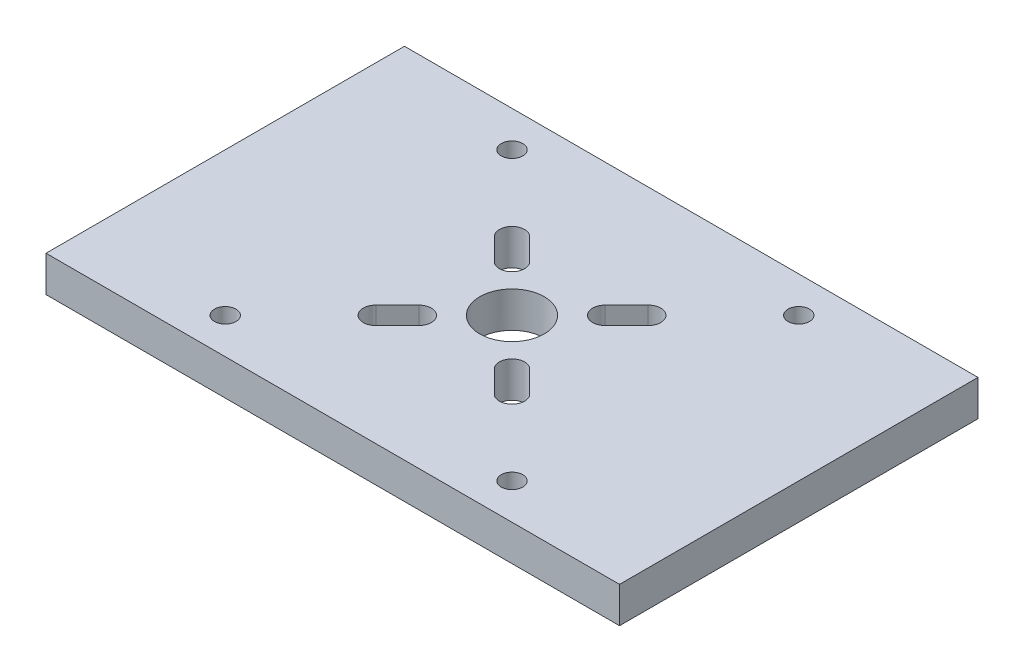
SolidWorks part; units mm, degrees
ref_plane "Front Plane" through (0, 0, 0) normal (0, 0, 1) x (1, 0, 0)
ref_plane "Top Plane" through (0, 0, 0) normal (0, 1, 0) x (1, 0, 0)
ref_plane "Right Plane" through (0, 0, 0) normal (1, 0, 0) x (0, 0, -1)
sketch "Sketch1" plane through (0, 0, 0) normal (0, 1, 0) x (1, 0, 0)
  line L1 (80, 50) -> (-80, 50)
  line L2 (80, 50) -> (80, -50)
  line L3 (80, -50) -> (-80, -50)
  line L4 (-80, 50) -> (-80, -50)
  line L5 (80, 50) -> (-80, -50) construction
  line L6 (80, -50) -> (-80, 50) construction
  point P0 (0, 0)
  dimension "D1" = 160
  dimension "D2" = 100
extrude "base" add sketch "Sketch1" along normal blind 10 contours L1 L4 L3 L2
sketch "Sketch2" plane through (0, 10, 0) normal (0, 1, 0) x (1, 0, 0)
  circle A0 centre (0, 0) radius 9
  dimension "D1" = 18
extrude "actuator cut" cut sketch "Sketch2" against normal blind 40
sketch "Sketch3" plane through (0, 10, 0) normal (0, 1, 0) x (1, 0, 0)
  line L0 (19, -19) -> (13, -13) construction
  line L1 (0, 0) -> (0, 19) construction
  line L2 (-19, -19) -> (19, 19) construction
  line L3 (-19, -19) -> (-13, -13) construction
  line L4 (-21.4749, -16.5251) -> (-15.4749, -10.5251)
  line L5 (-16.5251, -21.4749) -> (-10.5251, -15.4749)
  line L6 (21.4749, -16.5251) -> (15.4749, -10.5251)
  line L7 (16.5251, -21.4749) -> (10.5251, -15.4749)
  line L8 (0, 0) -> (19, 0) construction
  line L9 (19, 19) -> (13, 13) construction
  line L10 (21.4749, 16.5251) -> (15.4749, 10.5251)
  line L11 (16.5251, 21.4749) -> (10.5251, 15.4749)
  line L12 (-19, 19) -> (-13, 13) construction
  line L13 (-21.4749, 16.5251) -> (-15.4749, 10.5251)
  line L14 (-16.5251, 21.4749) -> (-10.5251, 15.4749)
  arc A4 (-21.4749, -16.5251) -> (-16.5251, -21.4749) centre (-19, -19) ccw
  arc A5 (-10.5251, -15.4749) -> (-15.4749, -10.5251) centre (-13, -13) ccw
  arc A6 (21.4749, -16.5251) -> (16.5251, -21.4749) centre (19, -19) cw
  arc A7 (10.5251, -15.4749) -> (15.4749, -10.5251) centre (13, -13) cw
  arc A8 (21.4749, 16.5251) -> (16.5251, 21.4749) centre (19, 19) ccw
  arc A9 (10.5251, 15.4749) -> (15.4749, 10.5251) centre (13, 13) ccw
  arc A10 (-21.4749, 16.5251) -> (-16.5251, 21.4749) centre (-19, 19) cw
  arc A11 (-10.5251, 15.4749) -> (-15.4749, 10.5251) centre (-13, 13) cw
  point P1 (-16, -16)
  point P10 (16, -16)
  point P20 (16, 16)
  point P27 (-16, 16)
  dimension "D5" = 3.5
  dimension "D4" = 19
  dimension "D1" = 13
  dimension "D2" = 19
  dimension "D3" = 45
  dimension "D6" = 19
extrude "Cut-Extrude1" cut sketch "Sketch3" against normal up to next
sketch "Sketch4" plane through (0, 0, 0) normal (0, -1, 0) x (1, 0, 0)
  line L0 (21.4749, 16.5251) -> (15.4749, 10.5251) construction
  line L1 (10.5251, 15.4749) -> (16.5251, 21.4749) construction
  line L2 (-15.4749, 10.5251) -> (-21.4749, 16.5251) construction
  line L3 (-16.5251, 21.4749) -> (-10.5251, 15.4749) construction
  line L4 (-10.5251, -15.4749) -> (-16.5251, -21.4749) construction
  line L5 (-21.4749, -16.5251) -> (-15.4749, -10.5251) construction
  line L6 (16.5251, -21.4749) -> (10.5251, -15.4749) construction
  line L7 (15.4749, -10.5251) -> (21.4749, -16.5251) construction
  line L8 (21.4749, 16.5251) -> (15.4749, 10.5251) construction
  line L9 (10.5251, 15.4749) -> (16.5251, 21.4749) construction
  line L10 (-15.4749, 10.5251) -> (-21.4749, 16.5251) construction
  line L11 (-16.5251, 21.4749) -> (-10.5251, 15.4749) construction
  line L12 (-10.5251, -15.4749) -> (-16.5251, -21.4749) construction
  line L13 (-21.4749, -16.5251) -> (-15.4749, -10.5251) construction
  line L14 (16.5251, -21.4749) -> (10.5251, -15.4749) construction
  line L15 (15.4749, -10.5251) -> (21.4749, -16.5251) construction
  line L16 (23.2426, 14.7574) -> (17.2426, 8.7574)
  line L17 (8.7574, 17.2426) -> (14.7574, 23.2426)
  line L18 (-17.2426, 8.7574) -> (-23.2426, 14.7574)
  line L19 (-14.7574, 23.2426) -> (-8.7574, 17.2426)
  line L20 (-8.7574, -17.2426) -> (-14.7574, -23.2426)
  line L21 (-23.2426, -14.7574) -> (-17.2426, -8.7574)
  line L22 (14.7574, -23.2426) -> (8.7574, -17.2426)
  line L23 (17.2426, -8.7574) -> (23.2426, -14.7574)
  arc A0 (10.5251, 15.4749) -> (15.4749, 10.5251) centre (13, 13) ccw construction
  arc A1 (21.4749, 16.5251) -> (16.5251, 21.4749) centre (19, 19) ccw construction
  arc A2 (-16.5251, 21.4749) -> (-21.4749, 16.5251) centre (-19, 19) ccw construction
  arc A3 (-15.4749, 10.5251) -> (-10.5251, 15.4749) centre (-13, 13) ccw construction
  arc A4 (-21.4749, -16.5251) -> (-16.5251, -21.4749) centre (-19, -19) ccw construction
  arc A5 (-10.5251, -15.4749) -> (-15.4749, -10.5251) centre (-13, -13) ccw construction
  arc A6 (15.4749, -10.5251) -> (10.5251, -15.4749) centre (13, -13) ccw construction
  arc A7 (16.5251, -21.4749) -> (21.4749, -16.5251) centre (19, -19) ccw construction
  arc A8 (10.5251, 15.4749) -> (15.4749, 10.5251) centre (13, 13) ccw construction
  arc A9 (21.4749, 16.5251) -> (16.5251, 21.4749) centre (19, 19) ccw construction
  arc A10 (-16.5251, 21.4749) -> (-21.4749, 16.5251) centre (-19, 19) ccw construction
  arc A11 (-15.4749, 10.5251) -> (-10.5251, 15.4749) centre (-13, 13) ccw construction
  arc A12 (-21.4749, -16.5251) -> (-16.5251, -21.4749) centre (-19, -19) ccw construction
  arc A13 (-10.5251, -15.4749) -> (-15.4749, -10.5251) centre (-13, -13) ccw construction
  arc A14 (15.4749, -10.5251) -> (10.5251, -15.4749) centre (13, -13) ccw construction
  arc A15 (16.5251, -21.4749) -> (21.4749, -16.5251) centre (19, -19) ccw construction
  arc A16 (8.7574, 17.2426) -> (17.2426, 8.7574) centre (13, 13) ccw
  arc A17 (23.2426, 14.7574) -> (14.7574, 23.2426) centre (19, 19) ccw
  arc A18 (-14.7574, 23.2426) -> (-23.2426, 14.7574) centre (-19, 19) ccw
  arc A19 (-17.2426, 8.7574) -> (-8.7574, 17.2426) centre (-13, 13) ccw
  arc A20 (-23.2426, -14.7574) -> (-14.7574, -23.2426) centre (-19, -19) ccw
  arc A21 (-8.7574, -17.2426) -> (-17.2426, -8.7574) centre (-13, -13) ccw
  arc A22 (17.2426, -8.7574) -> (8.7574, -17.2426) centre (13, -13) ccw
  arc A23 (14.7574, -23.2426) -> (23.2426, -14.7574) centre (19, -19) ccw
  dimension "D1" = 2.5
split line "Split Line1"
sketch "Sketch5" plane through (0, 10, 0) normal (0, 1, 0) x (1, 0, 0)
  line L0 (-40, 40) -> (-40, -40) construction
  line L1 (-40, -40) -> (40, -40) construction
  circle A0 centre (-40, -40) radius 3
  circle A1 centre (-40, 40) radius 3
  circle A2 centre (40, -40) radius 3
  circle A3 centre (40, 40) radius 3
  point P8 (-40, 0)
  point P9 (0, -40)
  dimension "D3" = 6
  dimension "D1" = 80
  dimension "D2" = 80
extrude "Cut-Extrude2" cut sketch "Sketch5" against normal up to next
sketch "Sketch6" plane through (0, 0, 0) normal (0, -1, 0) x (1, 0, 0)
  circle A0 centre (-40, 40) radius 4
  circle A1 centre (40, 40) radius 4
  circle A2 centre (40, -40) radius 4
  circle A3 centre (-40, -40) radius 4
  dimension "D1" = 8
extrude "Cut-Extrude3" cut sketch "Sketch6" against normal blind 5
equation "\"D4@Sketch3\"=\"D2@Sketch3\""
equation "\"D6@Sketch3\"=\"D2@Sketch3\""
